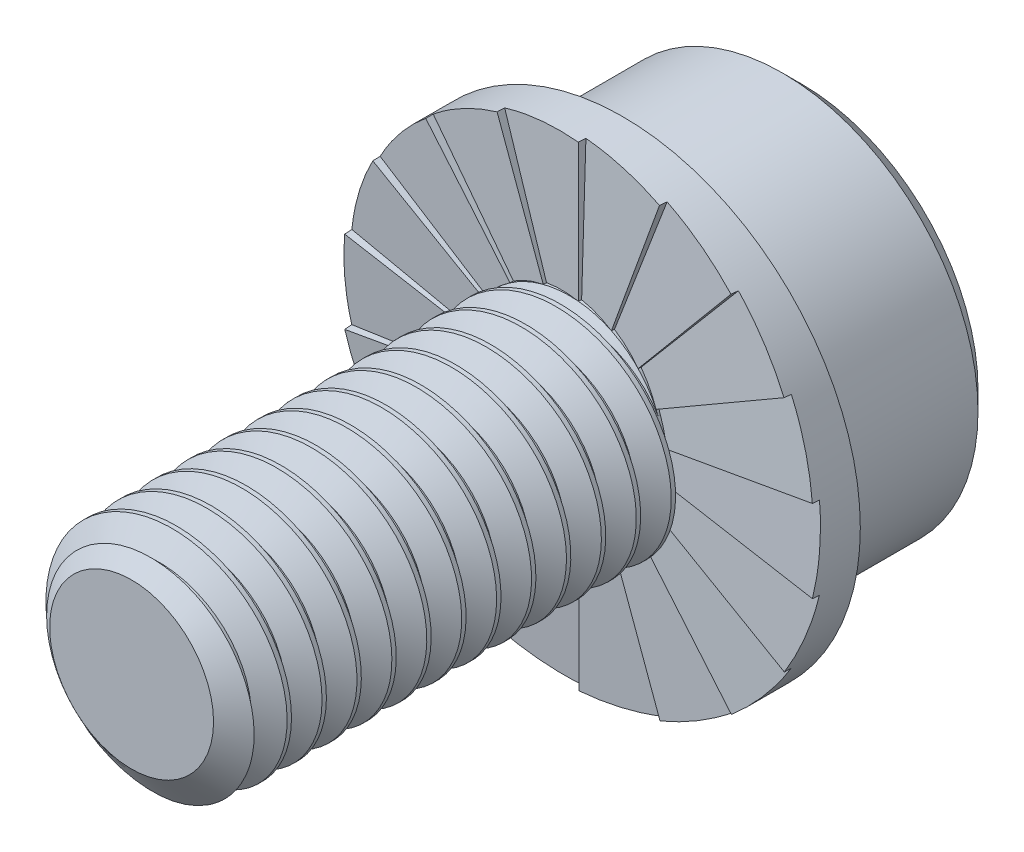
SolidWorks part; units mm, degrees
ref_plane "Front Plane" through (0, 0, 0) normal (0, 0, 1) x (1, 0, 0)
ref_plane "Top Plane" through (0, 0, 0) normal (0, 1, 0) x (1, 0, 0)
ref_plane "Right Plane" through (0, 0, 0) normal (1, 0, 0) x (0, 0, -1)
sketch "Sketch1" plane through (0, 0, 0) normal (0, 0, 1) x (1, 0, 0)
  circle A0 centre (0, 0) radius 4
  dimension "OD" = 8
extrude "Extrude1" add sketch "Sketch1" against normal blind 16
sketch "Sketch2" plane through (0, 0, 0) normal (0, 0, 1) x (1, 0, 0)
  circle A0 centre (0, 0) radius 4 construction
  circle A1 centre (0, 0) radius 4
curve "Helix/Spiral1" pitch 1.25 height 17.25 turns 13.8 parameters "pitch"=1.25
sketch "Sketch3" plane through (0, 0, 0) normal (1, 0, 0) x (0, 0, -1)
  line L0 (-1.0938, 4) -> (-0.625, 3.1881)
  line L1 (-0.625, 3.1881) -> (-0.4688, 3.1881)
  line L2 (-0.4688, 3.1881) -> (0, 4)
  line L3 (-1.0938, 4) -> (0, 4)
  line L4 (-0.5469, 4) -> (-0.5469, 3.1881) construction
  line L5 (-0.8594, 3.5941) -> (-0.2344, 3.5941) construction
  line L6 (0, 4) -> (0, -4) construction
  dimension "D1" = 0.1562
  dimension "D2" = 0.625
  dimension "D3" = 60
sweep "Cut-Sweep1" cut profiles "Sketch3" path "Helix/Spiral1"
sketch "Sketch4" plane through (0, 0, 0) normal (1, 0, 0) x (0, 0, -1)
  line L0 (0.7464, 4) -> (0, 2.9341)
  line L1 (0, 2.9341) -> (0, 4)
  line L2 (0.7464, 4) -> (0, 4)
  line L3 (-1.0938, 4) -> (0, 4) construction
  line L4 (0, 0) -> (7.0209, 0) construction
  dimension "D1" = 55
  dimension "D2" = 0.254
revolve "Cut-Revolve1" cut sketch "Sketch4" angle 360 about L4
sketch "Sketch5" plane through (0, 0, 0) normal (1, 0, 0) x (0, 0, -1)
  line L0 (16, -3.6352) -> (16, -0.9564) construction
  line L1 (16, 4.127) -> (0.1202, 4.127)
  line L2 (16, 4.127) -> (16, 0)
  line L3 (16, 0) -> (0, 0)
  line L4 (0, 3.7968) -> (0, 0)
  line L5 (0.1202, 4.127) -> (0, 3.7968)
  line L6 (0, 0) -> (9.9695, 0) construction
  point P3 (0, 4.127)
  point P10 (0, 4.127)
  dimension "D1" = 0.3302
  dimension "Thread min" = 0
  dimension "D2" = 0.127
  dimension "D3" = 20
revolve "partially thread" [suppressed] add sketch "Sketch5" angle 360 about L6
sketch "Sketch6" plane through (0, 0, -16) normal (0, 0, -1) x (-1, 0, 0)
  circle A0 centre (0, 0) radius 7
  dimension "head dia" = 14
extrude "Extrude2" add sketch "Sketch6" along normal blind 8 separate body
sketch "Sketch10" plane through (0, 0, -16) normal (0, 0, 1) x (1, 0, 0)
  circle A0 centre (0, 0) radius 8.5
  dimension "Flange Diameter" = 17
extrude "Boss-Extrude1" add sketch "Sketch10" against normal blind 1.5875
sketch "Sketch18" plane through (0, 0, -16) normal (0, 0, 1) x (1, 0, 0)
  line L0 (0, 0) -> (0, 8.5) construction
  circle A0 centre (0, 0) radius 8.5 construction
  circle A1 centre (0, 0) radius 8.5 construction
ref_plane "Plane4" through (1.3892, 0, -15.8785) normal (0.0872, 0, -0.9962) x (-0.9962, 0, -0.0872)
sketch "Sketch19" plane through (1.3892, 0, -15.8785) normal (0.0872, 0, -0.9962) x (-0.9962, 0, -0.0872)
  line L0 (1.3945, 0) -> (1.3945, 11.04)
  line L1 (1.3945, 0) -> (5.1691, 10.3707)
  spline S0 degree 3 poles (0.6662, -11.04) (2.1228, -11.04) (2.8389, -10.9682) (3.8955, -10.7573) (4.2447, -10.6697) (4.9371, -10.4589) (5.2811, -10.3353) (6.2816, -9.9188) (6.9142, -9.579) (7.8119, -8.977) (8.1037, -8.7599) (8.6643, -8.2978) (8.931, -8.0546) (9.692, -7.2902) (10.1472, -6.7341) (10.75, -5.8286) (10.9369, -5.5153) (11.2757, -4.8784) (11.5818, -4.228) (11.8234, -3.551) (12.0323, -2.8605) (12.1208, -2.5065) (12.3321, -1.4396) (12.4018, -0.7244) (12.4023, 0.3541) (12.385, 0.7146) (12.3144, 1.4376) (12.2612, 1.7974) (12.0512, 2.8577) (11.844, 3.5451) (11.4317, 4.5468) (11.2762, 4.8775) (10.9361, 5.5168) (10.7515, 5.826) (10.155, 6.7232) (9.7007, 7.281) (8.6746, 8.3127) (8.1176, 8.7711) (7.2236, 9.3719) (6.9156, 9.5578) (6.2788, 9.9003) (5.9486, 10.0574) (4.9472, 10.4743) (4.2603, 10.6837) (2.8484, 10.9671) (2.1178, 11.0397) (0.679, 11.0403) (-0.036, 10.9705) (-1.1017, 10.7585) (-1.456, 10.6696) (-2.1468, 10.4594) (-2.8236, 10.2163) (-3.473, 9.9086) (-4.1085, 9.5682) (-4.4209, 9.3806) (-5.3252, 8.7744) (-5.8798, 8.3171) (-6.6413, 7.5536) (-6.8834, 7.2861) (-7.3431, 6.7244) (-7.5596, 6.4315) (-8.159, 5.5314) (-8.4969, 4.8978) (-8.9108, 3.8971) (-9.0337, 3.5531) (-9.2436, 2.8598) (-9.3308, 2.5103) (-9.5409, 1.4533) (-9.6125, 0.7376) (-9.6138, -0.7168) (-9.5432, -1.4355) (-9.335, -2.4922) (-9.2484, -2.8414) (-9.0403, -3.5335) (-8.918, -3.8781) (-8.505, -4.8815) (-8.1679, -5.5157) (-7.3722, -6.7152) (-6.9082, -7.2842) (-5.8935, -8.305) (-5.3401, -8.7627) (-4.4397, -9.3689) (-4.1266, -9.5577) (-3.4903, -9.9001) (-3.1655, -10.0546) (-2.1716, -10.4694) (-1.4808, -10.6816) (-0.0545, -10.9682) (0.6662, -11.04) (2.1228, -11.04) (2.8389, -10.9682) knots -0.03125 -0.03125 0 0 0.03125 0.03125 0.046875 0.046875 0.0625 0.0625 0.09375 0.09375 0.109375 0.109375 0.125 0.125 0.15625 0.15625 0.171875 0.171875 0.1875 0.203125 0.203125 0.21875 0.21875 0.25 0.25 0.265625 0.265625 0.28125 0.28125 0.3125 0.3125 0.328125 0.328125 0.34375 0.34375 0.375 0.375 0.40625 0.40625 0.421875 0.421875 0.4375 0.4375 0.46875 0.46875 0.5 0.5 0.53125 0.53125 0.546875 0.546875 0.5625 0.578125 0.578125 0.59375 0.59375 0.625 0.625 0.640625 0.640625 0.65625 0.65625 0.6875 0.6875 0.703125 0.703125 0.71875 0.71875 0.75 0.75 0.78125 0.78125 0.796875 0.796875 0.8125 0.8125 0.84375 0.84375 0.875 0.875 0.90625 0.90625 0.921875 0.921875 0.9375 0.9375 0.96875 0.96875 1 1 1.03125 1.03125 1.046875 only from (1.3945, -11.04) to (1.3945, -11.04)
  spline S1 degree 3 poles (5.1691, 10.3707) (4.6425, 10.5636) (4.1042, 10.715) (2.8484, 10.9671) (2.1178, 11.0397) (1.3971, 11.04) (1.3958, 11.04) (1.3945, 11.04) knots 0.44441 0.44441 0.44441 0.44441 0.46875 0.46875 0.5 0.5 0.500057 0.500057 0.500057 0.500057
  dimension "D2" = 20
  dimension "D1" = 2.54
extrude "Cut-Extrude5" cut sketch "Sketch19" against normal blind 1.5875
pattern_circular "CirPattern1" count 18 over 360 about axis through (0, 0, 0) along (0, 0, 1) of "Cut-Extrude5"
sketch "Sketch20" plane through (0, 0, -16) normal (0, 0, -1) x (-1, 0, 0)
  arc A1 (-2.8471, 1.4346) -> (-3.0413, -0.9564) centre (0, 0) ccw
  arc A2 (-2.8471, 1.4346) -> (-3.0413, -0.9564) centre (0, 0) ccw
  arc A4 (3.5721, -1.8) -> (3.8158, 1.2) centre (0, 0) ccw
  arc A5 (3.5721, -1.8) -> (3.8158, 1.2) centre (0, 0) ccw
  spline S2 degree 3 poles (982.3645, 169.2644) (72.9039, 63.0094) (-10.3572, 11.0967) (-2.4743, -2.259) (-2.2476, -2.5341) (-1.7102, -3.0102) (-1.4115, -3.2012) (-0.7544, -3.4892) (-0.4097, -3.5797) (0.1237, -3.6342) (0.3038, -3.6393) (0.6592, -3.6247) (0.8358, -3.605) (1.1867, -3.5404) (1.3616, -3.4952) (1.6989, -3.3821) (1.8625, -3.314) (2.3385, -3.0757) (2.6372, -2.8688) (13.6084, 7.2796) (-30.8399, 84.8942) (-694.6031, -717.7264) knots -5.148956 -5.148956 -5.148956 -5.148956 0.125 0.125 0.25 0.25 0.375 0.375 0.5 0.5 0.5625 0.5625 0.625 0.625 0.6875 0.6875 0.75 0.75 0.875 0.875 6.021448 6.021448 6.021448 6.021448 only from (-3.0413, -0.9564) to (3.5721, -1.8)
  spline S3 degree 3 poles (-3.0413, -0.9564) (-2.9707, -1.3095) (-2.8393, -1.6406) (-2.4743, -2.259) (-2.2476, -2.5341) (-1.7102, -3.0102) (-1.4115, -3.2012) (-0.7544, -3.4892) (-0.4097, -3.5797) (0.1237, -3.6342) (0.3038, -3.6393) (0.6592, -3.6247) (0.8358, -3.605) (1.1867, -3.5404) (1.3616, -3.4952) (1.6989, -3.3821) (1.8625, -3.314) (2.3385, -3.0757) (2.6372, -2.8688) (3.1575, -2.3875) (3.3851, -2.1069) (3.5721, -1.8) knots 0 0 0 0 0.125 0.125 0.25 0.25 0.375 0.375 0.5 0.5 0.5625 0.5625 0.625 0.625 0.6875 0.6875 0.75 0.75 0.875 0.875 1 1 1 1
  spline S4 degree 3 poles (901.947, 440.9261) (-348.8865, -299.7761) (24.5362, -25.5153) (3.1774, 2.2639) (3.0571, 2.3992) (2.8016, 2.6478) (2.666, 2.7621) (2.2364, 3.0749) (1.9144, 3.2451) (1.4128, 3.4241) (1.2417, 3.4717) (0.8918, 3.5425) (0.7123, 3.5655) (0.3568, 3.5854) (0.1795, 3.5826) (-0.1745, 3.5518) (-0.3526, 3.5221) (-0.8739, 3.3916) (-1.2001, 3.2526) (-1.8091, 2.869) (-2.0768, 2.6336) (-2.4197, 2.2187) (-2.5231, 2.071) (-8.6617, -8.3734) (37.7883, -48.4753) (848.733, -522.6964) knots -12.112463 -12.112463 -12.112463 -12.112463 0.125 0.125 0.1875 0.1875 0.25 0.25 0.375 0.375 0.4375 0.4375 0.5 0.5 0.5625 0.5625 0.625 0.625 0.75 0.75 0.875 0.875 0.9375 0.9375 5.120504 5.120504 5.120504 5.120504 only from (3.8158, 1.2) to (-2.8471, 1.4346)
  spline S5 degree 3 poles (3.8158, 1.2) (3.6789, 1.5324) (3.503, 1.8405) (3.1774, 2.2639) (3.0571, 2.3992) (2.8016, 2.6478) (2.666, 2.7621) (2.2364, 3.0749) (1.9144, 3.2451) (1.4128, 3.4241) (1.2417, 3.4717) (0.8918, 3.5425) (0.7123, 3.5655) (0.3568, 3.5854) (0.1795, 3.5826) (-0.1745, 3.5518) (-0.3526, 3.5221) (-0.8739, 3.3916) (-1.2001, 3.2526) (-1.8091, 2.869) (-2.0768, 2.6336) (-2.4197, 2.2187) (-2.5231, 2.071) (-2.7039, 1.7635) (-2.7825, 1.6031) (-2.8471, 1.4346) knots 0 0 0 0 0.125 0.125 0.1875 0.1875 0.25 0.25 0.375 0.375 0.4375 0.4375 0.5 0.5 0.5625 0.5625 0.625 0.625 0.75 0.75 0.875 0.875 0.9375 0.9375 1 1 1 1
  dimension "D1" = 0
extrude "Boss-Extrude2" add sketch "Sketch20" along normal up to next
sketch "Sketch7" plane through (0, 0, -24) normal (0, 0, -1) x (-1, 0, 0)
  line L1 (0, 3.4641) -> (-3, 1.7321)
  line L2 (-3, 1.7321) -> (-3, -1.7321)
  line L3 (-3, -1.7321) -> (0, -3.4641)
  line L4 (0, -3.4641) -> (3, -1.7321)
  line L5 (3, -1.7321) -> (3, 1.7321)
  line L6 (3, 1.7321) -> (0, 3.4641)
  circle A0 centre (0, 0) radius 3 construction
  dimension "hex dia" = 6
extrude "Cut-Extrude1" cut sketch "Sketch7" against normal blind 4.5
sketch "Sketch8" plane through (0, 0, -24) normal (0, 0, -1) x (-1, 0, 0)
  circle A0 centre (0, 0) radius 3.4641
extrude "Cut-Extrude2" cut sketch "Sketch8" against normal through all draft 45
chamfer "Chamfer1" distance 0.7 angle 45 1 edges at (-7, 0, -24)
sketch "Sketch9" plane through (0, 0, 0) normal (1, 0, 0) x (0, 0, -1)
  line L0 (0, 4) -> (0, -4) construction
  line L1 (6.875, 4) -> (6.875, -4) construction
  line L2 (0, -4) -> (6.875, -4) construction
  line L3 (0, 4) -> (6.875, 4) construction
  dimension "D1" = 6.875
fillet "Fillet1" radius 0.3969 1 edges at (7, 0, -17.5875)
equation "\"D3@Helix/Spiral1\" = \"screw length@Extrude1\"+\"pitch@Helix/Spiral1\""
equation "\"D1@Sketch3\" = \"pitch@Helix/Spiral1\"*.125"
equation "\"D2@Sketch3\" = \"pitch@Helix/Spiral1\"*.5"
equation "\"D1@Cut-Extrude1\" = \"hex dia@Sketch7\"*.75"
equation "\"D1@Chamfer1\" = \"head dia@Sketch6\"*.05"
equation "\"D1@Sketch9\" = \"pitch@Helix/Spiral1\"*5.5"
